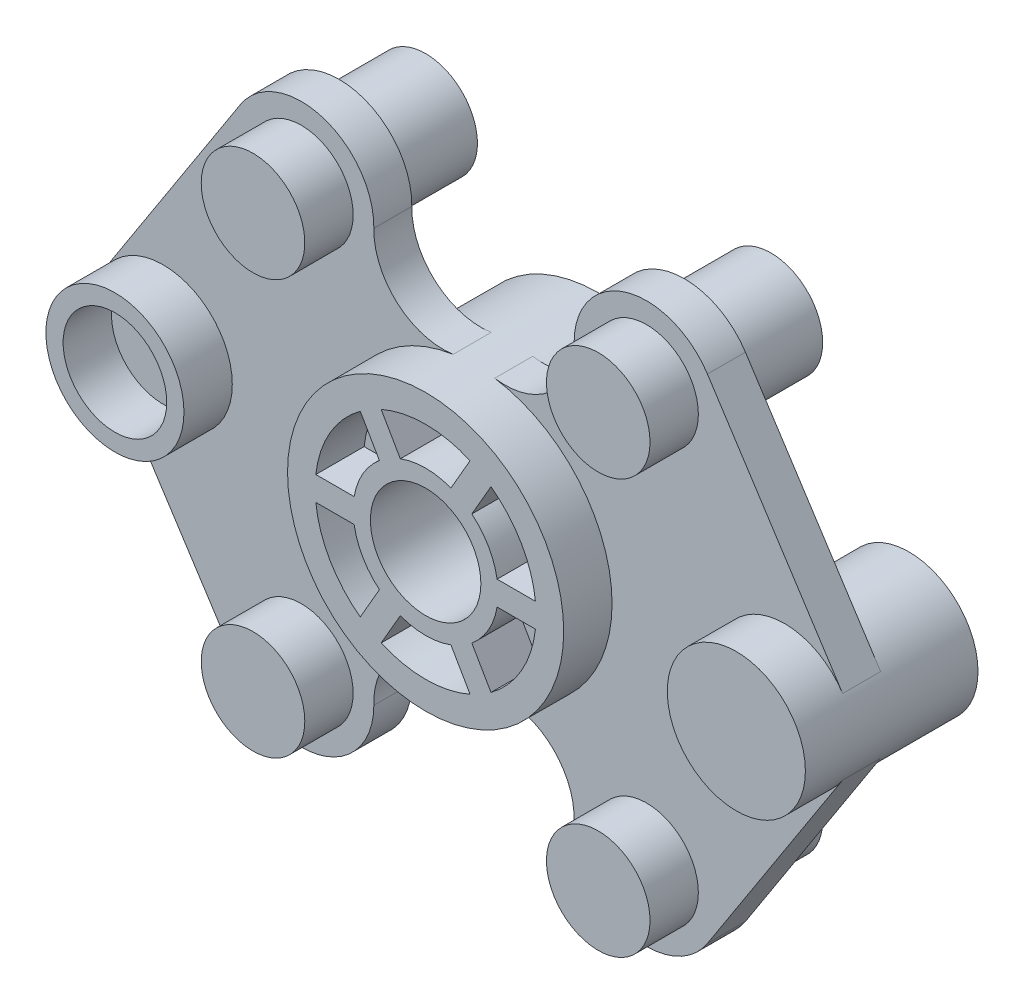
SolidWorks part; units mm, degrees
ref_plane "Front Plane" through (0, 0, 0) normal (0, 0, 1) x (1, 0, 0)
ref_plane "Top Plane" through (0, 0, 0) normal (0, 1, 0) x (1, 0, 0)
ref_plane "Right Plane" through (0, 0, 0) normal (1, 0, 0) x (0, 0, -1)
sketch "Sketch1" plane through (0, 0, 0) normal (0, 0, 1) x (1, 0, 0)
  line L0 (0, -80.4574) -> (0, 80.4574) construction
  line L1 (0, 80.4574) -> (0, 0) construction
  line L2 (-21, 0) -> (-54.1746, 0) construction
  line L3 (-54.1746, 0) -> (-170.6686, 0) construction
  line L4 (0, 0) -> (37.3564, 0) construction
  line L5 (37.3564, 0) -> (146.538, 0) construction
  line L6 (20.7073, 3.4938) -> (31.8087, 3.4938)
  line L7 (20.7073, -3.4938) -> (31.8087, -3.4938)
  line L8 (13.3794, -16.1862) -> (18.9301, -25.8002)
  line L9 (7.3279, -19.68) -> (12.8786, -29.2941)
  line L10 (-7.3279, -19.68) -> (-12.8786, -29.2941)
  line L11 (-13.3794, -16.1862) -> (-18.9301, -25.8002)
  line L12 (-20.7073, -3.4938) -> (-31.8087, -3.4938)
  line L13 (-20.7073, 3.4938) -> (-31.8087, 3.4938)
  line L14 (-13.3794, 16.1862) -> (-18.9301, 25.8002)
  line L15 (-7.3279, 19.68) -> (-12.8786, 29.2941)
  line L16 (7.3279, 19.68) -> (12.8786, 29.2941)
  line L17 (13.3794, 16.1862) -> (18.9301, 25.8002)
  line L18 (67.6329, 71.4053) -> (106.7933, 10.8622)
  line L19 (106.7933, -10.8622) -> (67.6329, -71.4053)
  line L20 (-106.7933, -10.8622) -> (-67.6329, -71.4053)
  line L21 (-67.6329, 71.4053) -> (-106.7933, 10.8622)
  line L22 (-20.7073, -3.4938) -> (-31.8087, -3.4938)
  line L23 (-20.7073, 3.4938) -> (-31.8087, 3.4938)
  arc A0 (20.7073, 3.4938) -> (13.3794, 16.1862) centre (0, 0) ccw
  circle A1 centre (0, 0) radius 16
  arc A2 (31.8087, 3.4938) -> (18.9301, 25.8002) centre (0, 0) ccw
  circle A3 centre (0, 0) radius 40
  arc A4 (7.3279, 19.68) -> (-7.3279, 19.68) centre (0, 0) ccw
  arc A5 (12.8786, 29.2941) -> (-12.8786, 29.2941) centre (0, 0) ccw
  arc A6 (-18.9301, 25.8002) -> (-31.8087, 3.4938) centre (0, 0) ccw
  arc A7 (-13.3794, 16.1862) -> (-20.7073, 3.4938) centre (0, 0) ccw
  arc A8 (-31.8087, -3.4938) -> (-18.9301, -25.8002) centre (0, 0) ccw
  arc A9 (-20.7073, -3.4938) -> (-13.3794, -16.1862) centre (0, 0) ccw
  arc A10 (13.3794, -16.1862) -> (20.7073, -3.4938) centre (0, 0) ccw
  arc A11 (18.9301, -25.8002) -> (31.8087, -3.4938) centre (0, 0) ccw
  arc A12 (-7.3279, -19.68) -> (7.3279, -19.68) centre (0, 0) ccw
  arc A13 (-12.8786, -29.2941) -> (12.8786, -29.2941) centre (0, 0) ccw
  circle A14 centre (90, 0) radius 20
  circle A15 centre (90, 0) radius 15
  circle A16 centre (50, 60) radius 15
  arc A17 (67.6329, 71.4053) -> (29.0029, 59.6519) centre (50, 60) ccw
  arc A18 (67.6329, -71.4053) -> (29.0116, -59.3028) centre (50, -60) cw
  circle A19 centre (50, -60) radius 15
  circle A20 centre (-50, -60) radius 15
  arc A21 (-70.0824, -66.1398) -> (-29.0116, -59.3028) centre (-50, -60) ccw
  circle A22 centre (-50, 60) radius 15
  circle A23 centre (-90, 0) radius 15
  circle A24 centre (-90, 0) radius 20
  arc A25 (-70.0824, 66.1398) -> (-29.0029, 59.6519) centre (-50, 60) cw
  arc A26 (29.0029, 59.6519) -> (6.0038, 39.5469) centre (9.0056, 59.3203) cw
  arc A27 (6.0077, -39.5463) -> (29, -60) centre (9.0116, -59.3194) cw
  circle A28 centre (-50, -60) radius 15
  arc A29 (-70.0824, -66.1398) -> (-29.0116, -59.3028) centre (-50, -60) ccw
  arc A30 (-70.0824, 66.1398) -> (-29.0029, 59.6519) centre (-50, 60) cw
  circle A31 centre (-50, 60) radius 15
  circle A32 centre (-90, 0) radius 15
  circle A33 centre (-90, 0) radius 20
  arc A34 (-18.9301, -25.8002) -> (-31.8087, -3.4938) centre (0, 0) cw
  arc A35 (-31.8087, 3.4938) -> (-18.9301, 25.8002) centre (0, 0) cw
  arc A36 (-29.0029, 59.6519) -> (-6.0038, 39.5469) centre (-9.0056, 59.3203) ccw
  arc A37 (-6.0077, -39.5463) -> (-29, -60) centre (-9.0116, -59.3194) ccw
  point P9 (0, 0)
  point P38 (0, 0)
  dimension "D1" = 32
  dimension "D2" = 42
  dimension "D3" = 64
  dimension "D4" = 80
  dimension "D6" = 30
  dimension "D7" = 40
  dimension "D8" = 30
  dimension "D9" = 42
  dimension "D13" = 20
  dimension "D14" = 20
  dimension "D10" = 50
  dimension "D11" = 60
  dimension "D12" = 90
  dimension "D5" = 6
extrude "Boss-Extrude1" add sketch "Sketch1" along normal blind 11 contours A7 L14 A6 L13 | L16 A5 L15 A4 | L6 A2 L17 A0 | L8 A11 L7 A10 | A9 L12 A8 L11 | L10 A13 L9 A12 | A37 A3 A36 A25 L21 A24 L20 A21 A20 A22 | A3 A27 A18 L19 A14 L18 A17 A26 A16 A19 | A22 | A24 region at (22.7902, 13.1579, 0) region at (22.7902, -13.1579, 0) region at (0, -26.3159, 0) region at (-22.7902, -13.1579, 0) region at (-22.7902, 13.1579, 0) region at (0, 26.3159, 0) region at (56.9781, 0.0011, 0) region at (-56.9781, 0.0011, 0) region at (-50, 60, 0)
extrude "Boss-Extrude2" add sketch "Sketch1<3>" along normal mid plane 50 contours A16 | A19 | A20 | A24 A23 | A3 A13 L10 A12 L9 A11 L8 A10 L7 A5 L16 A4 L15 A1 A2 L6 A0 L17 L14 A7 L13 A6 L12 A9 L11 A8 | A14 | A22 region at (29.4748, 25.3378, 0) region at (-84.4974, 18.639, 0) region at (50, 60, 0) region at (50, -60, 0) region at (-50, -60, 0)
sketch "Sketch1<3>" plane through (0, 0, 0) normal (0, 0, 1) x (1, 0, 0) same geometry as "Sketch1"
